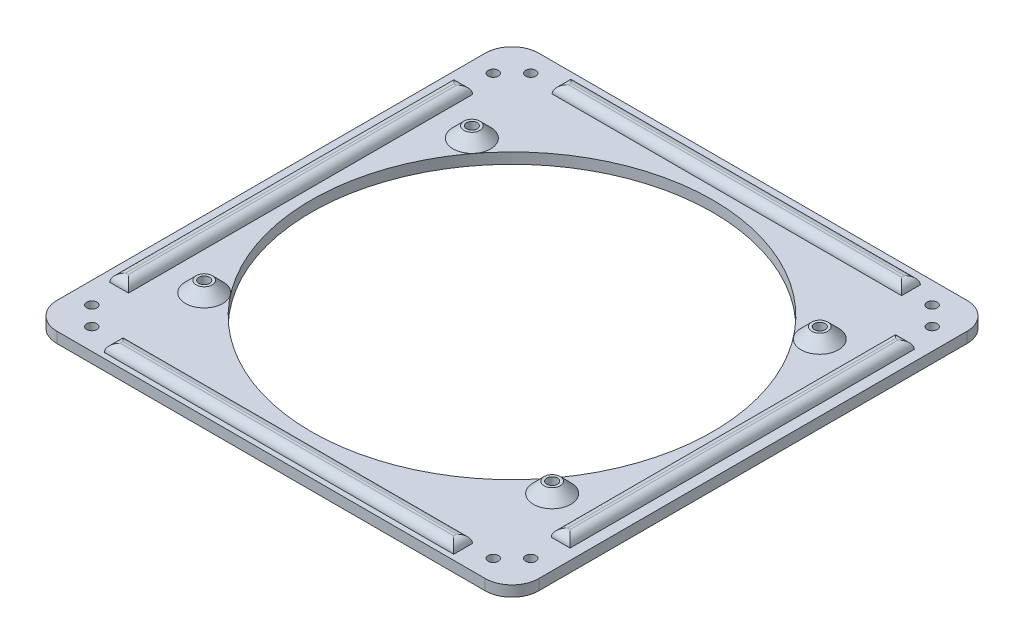
SolidWorks part; units mm, degrees
ref_plane "Спереди" through (0, 0, 0) normal (0, 0, 1) x (1, 0, 0)
ref_plane "Сверху" through (0, 0, 0) normal (0, 1, 0) x (1, 0, 0)
ref_plane "Справа" through (0, 0, 0) normal (1, 0, 0) x (0, 0, -1)
sketch "Эскиз1" plane through (0, 0, 0) normal (0, 1, 0) x (1, 0, 0)
  line L1 (-90, -90) -> (90, -90)
  line L2 (-90, -90) -> (-90, 90)
  line L3 (-90, 90) -> (90, 90)
  line L4 (90, -90) -> (90, 90)
  line L5 (-90, -90) -> (90, 90) construction
  line L6 (-90, 90) -> (90, -90) construction
  line L7 (-82, -75) -> (82, -75) construction
  line L8 (-82, -75) -> (-82, 75) construction
  line L9 (-82, 75) -> (82, 75) construction
  line L10 (82, -75) -> (82, 75) construction
  line L11 (0, 75) -> (0, -75) construction
  line L12 (-82, 0) -> (82, 0) construction
  line L13 (-75, -82) -> (75, -82) construction
  line L14 (-75, -82) -> (-75, 82) construction
  line L15 (-75, 82) -> (75, 82) construction
  line L16 (75, -82) -> (75, 82) construction
  line L17 (0, 82) -> (0, -82) construction
  line L18 (-75, 0) -> (75, 0) construction
  circle A0 centre (75, 82) radius 1.9
  circle A1 centre (82, 75) radius 1.9
  circle A2 centre (-82, 75) radius 1.9
  circle A3 centre (-75, 82) radius 1.9
  circle A4 centre (-82, -75) radius 1.9
  circle A5 centre (-75, -82) radius 1.9
  circle A6 centre (75, -82) radius 1.9
  circle A7 centre (82, -75) radius 1.9
  circle A8 centre (0, 0) radius 75
  point P0 (0, 0)
  point P6 (0, 0)
  point P10 (0, 0)
  dimension "D6" = 3.8
  dimension "D7" = 3.8
  dimension "D8" = 150
  dimension "D1" = 180
  dimension "D2" = 164
  dimension "D3" = 150
  dimension "D4" = 150
  dimension "D5" = 164
extrude "Бобышка-Вытянуть1" add sketch "Эскиз1" along normal blind 4
fillet "Скругление1" radius 10 4 edges at (90, 2, 90) (-90, 2, 90) (-90, 2, -90) (90, 2, -90)
sketch "Эскиз2" plane through (0, 4, 0) normal (0, 1, 0) x (1, 0, 0)
  line L1 (-65, -50) -> (65, -50) construction
  line L2 (-65, -50) -> (-65, 50) construction
  line L3 (-65, 50) -> (65, 50) construction
  line L4 (65, -50) -> (65, 50) construction
  line L5 (0, 50) -> (0, -50) construction
  line L6 (-65, 0) -> (65, 0) construction
  circle A0 centre (-65, 50) radius 3
  circle A1 centre (65, 50) radius 3
  circle A2 centre (65, -50) radius 3
  circle A3 centre (-65, -50) radius 3
  circle A4 centre (-65, 50) radius 2
  circle A5 centre (65, 50) radius 2
  circle A6 centre (65, -50) radius 2
  circle A7 centre (-65, -50) radius 2
  point P0 (0, 0)
  dimension "D3" = 6
  dimension "D4" = 4
  dimension "D1" = 130
  dimension "D2" = 100
extrude "Бобышка-Вытянуть2" add sketch "Эскиз2" along normal blind 4
chamfer "Фаска1" distance 4 angle 45 4 edges at (-65, 4, -53) (-65, 4, 47) (65, 4, 47) (65, 4, -53)
sketch "Эскиз3" plane through (0, 8, 0) normal (0, 1, 0) x (1, 0, 0)
  line L0 (0, 22.6622) -> (0, 0) construction
  line L1 (0, 0) -> (14.7055, 0) construction
  circle A0 centre (-65, 50) radius 2
  circle A1 centre (65, 50) radius 2
  circle A2 centre (65, -50) radius 2
  circle A3 centre (-65, -50) radius 2
extrude "Вырез-Вытянуть1" cut sketch "Эскиз3" against normal blind 7
sketch "Эскиз4" plane through (0, 4, 0) normal (0, 1, 0) x (1, 0, 0)
  line L0 (0, 42.1823) -> (0, -0.8727) construction
  line L1 (-86, -64.3006) -> (-79, -64.3006)
  line L2 (-86, -64.3006) -> (-86, 64.3006)
  line L3 (-86, 64.3006) -> (-79, 64.3006)
  line L4 (-79, -64.3006) -> (-79, 64.3006)
  line L5 (-82.5, 64.3006) -> (-82.5, -64.3006) construction
  line L6 (-86, 0) -> (-79, 0) construction
  line L7 (0, -0.8727) -> (59.8698, -0.8727) construction
  line L8 (86, 64.3006) -> (79, 64.3006)
  line L9 (79, -64.3006) -> (79, 64.3006)
  line L10 (86, -64.3006) -> (79, -64.3006)
  line L11 (86, -64.3006) -> (86, 64.3006)
  line L12 (-64.2917, -81.0392) -> (66.2699, -81.0392)
  line L13 (-64.2917, 86.2937) -> (66.2699, 86.2937)
  line L14 (-64.2917, 86.2937) -> (-64.2917, 79.2937)
  line L15 (-64.2917, 79.2937) -> (66.2699, 79.2937)
  line L16 (66.2699, 86.2937) -> (66.2699, 79.2937)
  line L17 (0.9891, 79.2937) -> (0.9891, 86.2937) construction
  line L18 (-64.2917, 82.7937) -> (66.2699, 82.7937) construction
  line L19 (66.2699, -88.0392) -> (66.2699, -81.0392)
  line L20 (-64.2917, -88.0392) -> (66.2699, -88.0392)
  line L21 (-64.2917, -88.0392) -> (-64.2917, -81.0392)
  line L22 (-64.2917, -84.5392) -> (66.2699, -84.5392) construction
  line L23 (0.9891, -81.0392) -> (0.9891, -88.0392) construction
  line L24 (90, -80) -> (90, 80) construction
  point P0 (-82.5, 0)
  point P11 (0.9891, 82.7937)
  point P19 (0.9891, -84.5392)
  dimension "D1" = 4
  dimension "D2" = 11
extrude "Бобышка-Вытянуть3" add sketch "Эскиз4" along normal blind 3
fillet "Скругление2" radius 3 16 edges at (-82.5, 7, 64.3006) (-86, 7, 0) (-82.5, 7, -64.3006) (-79, 7, 0) (0.9891, 7, 81.0392) (66.2699, 7, 84.5392) (0.9891, 7, 88.0392) (-64.2917, 7, 84.5392) (82.5, 7, 64.3006) (79, 7, 0) (82.5, 7, -64.3006) (86, 7, 0) (0.9891, 7, -79.2937) (-64.2917, 7, -82.7937) (0.9891, 7, -86.2937) (66.2699, 7, -82.7937)
